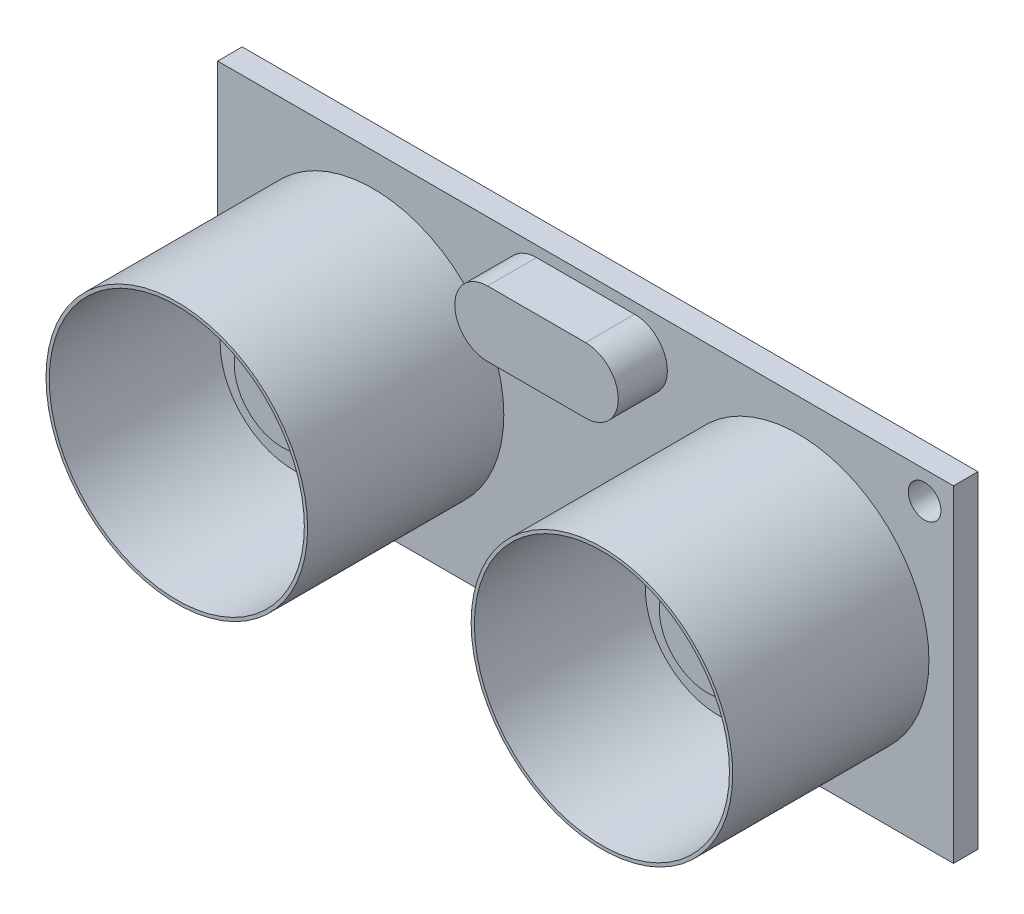
SolidWorks part; units mm, degrees
ref_plane "Alzado" through (0, 0, 0) normal (0, 0, 1) x (1, 0, 0)
ref_plane "Planta" through (0, 0, 0) normal (0, 1, 0) x (1, 0, 0)
ref_plane "Vista lateral" through (0, 0, 0) normal (1, 0, 0) x (0, 0, -1)
sketch "Croquis1" plane through (0, 0, 0) normal (0, 0, 1) x (1, 0, 0)
  line L1 (22.5, -6.65) -> (-22.5, -6.65)
  line L2 (22.5, -6.65) -> (22.5, 13.35)
  line L3 (22.5, 13.35) -> (-22.5, 13.35)
  line L4 (-22.5, -6.65) -> (-22.5, 13.35)
  circle A0 centre (20.7331, 11.6574) radius 1
  circle A1 centre (-20.2669, -4.8426) radius 1
  point P0 (0, 0)
  dimension "D4" = 2
  dimension "D5" = 2
  dimension "D1" = 45
  dimension "D2" = 20
  dimension "D3" = 41
  dimension "D6" = 16.5
extrude "Saliente-Extruir1" add sketch "Croquis1" along normal blind 1.5
sketch "Croquis2" plane through (0, 0, 1.5) normal (0, 0, 1) x (1, 0, 0)
  circle A0 centre (-13, 3.35) radius 8
  circle A1 centre (13, 3.35) radius 8
  dimension "D1" = 16
  dimension "D2" = 26
extrude "Saliente-Extruir2" add sketch "Croquis2" along normal blind 12
sketch "Croquis4" plane through (0, 0, 0) normal (0, 0, -1) x (-1, 0, 0)
  line L0 (0, 0) -> (0, -15.7145) construction
  line L1 (22.5, -6.65) -> (-22.5, -6.65) construction
  line L2 (-2, -4.65) -> (2, -4.65)
  line L3 (-2, -4.65) -> (-2, -6.65)
  line L4 (-2, -6.65) -> (2, -6.65)
  line L5 (0, -4.65) -> (0, -6.65)
  line L6 (2, -4.65) -> (2, -6.65)
  line L8 (-2, -4.65) -> (-4, -4.65)
  line L9 (-2, -4.65) -> (-2, -6.65)
  line L10 (-2, -6.65) -> (-4, -6.65)
  line L11 (-4, -4.65) -> (-4, -6.65)
  line L12 (2, -4.65) -> (4, -4.65)
  line L13 (2, -4.65) -> (2, -6.65)
  line L14 (2, -6.65) -> (4, -6.65)
  line L15 (4, -4.65) -> (4, -6.65)
  line M11 (-22.5, -6.65) -> (22.5, -6.65)
  dimension "D1" = 2
  dimension "D2" = 2
  dimension "D3" = 2
  dimension "D4" = 2
extrude "Saliente-Extruir4" add sketch "Croquis4" along normal blind 2 contours L8 L11 L3 M11 | L15 L12 L6 M11 | L6 L2 L5 L4 | L5 L2 L3 M11 region at (1, -5.65, 0) region at (3, -5.65, 0) region at (-1, -5.65, 0) region at (-3, -5.65, 0)
ref_plane "Plano1" through (0, 0, 0) normal (-1, 0, 0) x (0, 0, 1)
ref_plane "Plano2" through (-1, 0, 0) normal (-1, 0, 0) x (0, 0, 1)
sketch "Croquis5" plane through (-1, 0, 0) normal (-1, 0, 0) x (0, 0, 1)
  line L0 (-2, -5.15) -> (-3, -5.15)
  line L1 (-2, -4.65) -> (-2, -6.65) construction
  line L2 (-3, -5.15) -> (-3, -12.15)
  line L3 (-3, -12.15) -> (-2.5, -12.15)
  line L4 (-2.5, -12.15) -> (-2.5, -6.15)
  line L5 (-2.5, -6.15) -> (-2, -6.15)
  line L8 (-2, -4.65) -> (0, -4.65) construction
  line L9 (-2, -6.65) -> (0, -6.65) construction
  line L10 (-2, -5.15) -> (-2, -6.15)
  dimension "D1" = 0.5
  dimension "D2" = 0.5
  dimension "D3" = 1
  dimension "D4" = 0.5
  dimension "D5" = 7
extrude "Saliente-Extruir5" [suppressed] add sketch "Croquis5" along normal blind 0.5 and the other way blind 0.5
pattern_linear "MatrizL1" [suppressed] count 2 spacing 2 count 3 spacing 2 of bodies 105
fillet "Redondeo1" [suppressed] radius 0.5
fillet "Redondeo2" [suppressed] radius 0.2
fillet "Redondeo3" radius 0.2 4 edges at (4, -4.65, -1) (4, -6.65, -1) (-4, -6.65, -1) (-4, -4.65, -1)
sketch "Croquis6" plane through (0, 0, 1.5) normal (0, 0, 1) x (1, 0, 0)
  line L0 (-3, 10.6897) -> (3, 10.6897) construction
  line L1 (-3, 12.6897) -> (3, 12.6897)
  line L2 (-3, 8.6897) -> (3, 8.6897)
  arc A0 (-3, 12.6897) -> (-3, 8.6897) centre (-3, 10.6897) ccw
  arc A1 (3, 8.6897) -> (3, 12.6897) centre (3, 10.6897) ccw
  point P2 (0, 10.6897)
  point P7 (-5, 10.6897)
  point P8 (5, 10.6897)
  dimension "D1" = 10
  dimension "D2" = 4
extrude "Saliente-Extruir6" add sketch "Croquis6" along normal blind 3
sketch "Croquis7" plane through (0, 0, 1.5) normal (0, 0, 1) x (1, 0, 0)
  text T0 "HC-SR04" font "Century Gothic" height in points 7
shell "Vaciado1" thickness 0.2 removed face at (5, 3.35, 13.5)
sketch "Croquis9" plane through (0, 0, 0.2) normal (0, 0, 1) x (1, 0, 0)
  circle A0 centre (13, 3.35) radius 4.5
  dimension "D1" = 9
extrude "Saliente-Extruir8" add sketch "Croquis9" along normal blind 6.15
sketch "Croquis10" plane through (0, 0, 6.35) normal (0, 0, 1) x (1, 0, 0)
  circle A0 centre (13, 3.35) radius 2.5
  dimension "D1" = 5
extrude "Saliente-Extruir9" add sketch "Croquis10" along normal blind 0.68 draft 34 draft outward yes
sketch "Croquis12" plane through (0, 0, 13.5) normal (0, 0, 1) x (1, 0, 0)
  circle A0 centre (-13, 3.35) radius 7.8
  circle A1 centre (-13, 3.35) radius 8 construction
  dimension "D1" = 0.2
extrude "Cortar-Extruir1" cut sketch "Croquis12" against normal blind 12
mirror "Simetría3" about plane through (0, 0, 0) normal (1, 0, 0) of "Saliente-Extruir9", "Saliente-Extruir8"
